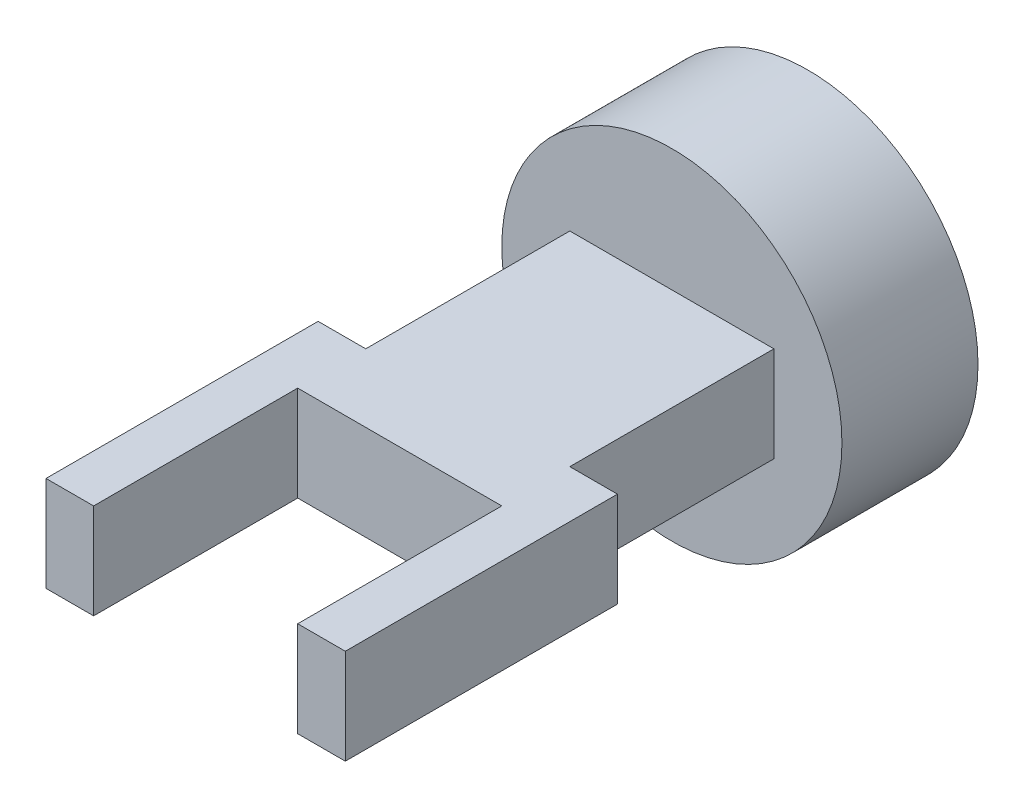
SolidWorks part; units mm, degrees
ref_plane "Front Plane" through (0, 0, 0) normal (0, 0, 1) x (1, 0, 0)
ref_plane "Top Plane" through (0, 0, 0) normal (0, 1, 0) x (1, 0, 0)
ref_plane "Right Plane" through (0, 0, 0) normal (1, 0, 0) x (0, 0, -1)
sketch "Sketch1" plane through (0, 0, 0) normal (0, 0, 1) x (1, 0, 0)
  circle A0 centre (0, 0) radius 12.5
  dimension "D1" = 25
extrude "Boss-Extrude1" add sketch "Sketch1" along normal blind 10
sketch "Sketch2" plane through (0, 0, 10) normal (0, 0, 1) x (1, 0, 0)
  line L1 (7.5, -3.5) -> (-7.5, -3.5)
  line L2 (7.5, -3.5) -> (7.5, 3.5)
  line L3 (7.5, 3.5) -> (-7.5, 3.5)
  line L4 (-7.5, -3.5) -> (-7.5, 3.5)
  line L5 (7.5, -3.5) -> (-7.5, 3.5) construction
  line L6 (7.5, 3.5) -> (-7.5, -3.5) construction
  point P0 (0, 0)
  dimension "D1" = 7
  dimension "D2" = 15
extrude "Boss-Extrude2" add sketch "Sketch2" along normal blind 20
sketch "Sketch3" plane through (0, 0, 30) normal (0, 0, 1) x (1, 0, 0)
  line L0 (0, 3.5) -> (0, -3.5)
  line L1 (7.5, 3.5) -> (-7.5, 3.5) construction
  line L2 (-7.5, -3.5) -> (7.5, -3.5) construction
  line L3 (-7.5, 3.5) -> (-7.5, -3.5)
  line L10 (7.5, 3.5) -> (7.5, -3.5)
  line L12 (-11, 3.5) -> (-11, -3.5)
  line L13 (-7.5, 3.5) -> (-11, 3.5)
  line L14 (-11, -3.5) -> (-7.5, -3.5)
  line L15 (7.5, 3.5) -> (11, 3.5)
  line L16 (11, 3.5) -> (11, -3.5)
  line L17 (11, -3.5) -> (7.5, -3.5)
  line M6 (-7.5, 3.5) -> (-7.5, -3.5)
  line M8 (7.5, -3.5) -> (7.5, 3.5)
  dimension "D1" = 3.5
extrude "Boss-Extrude4" add sketch "Sketch3" along normal blind 15 separate body contours L12 L14 L13 M6 | L17 L16 L15 M8 region at (-9.25, 0, 30) region at (9.25, 0, 30)
extrude "Boss-Extrude5" add sketch "Sketch3<4>" against normal blind 5 contours L12 L14 L13 M6 | L17 L16 L15 M8 region at (-9.25, 0, 30) region at (9.25, 0, 30)
sketch "Sketch3<4>" plane through (0, 0, 30) normal (0, 0, 1) x (1, 0, 0) same geometry as "Sketch3"
